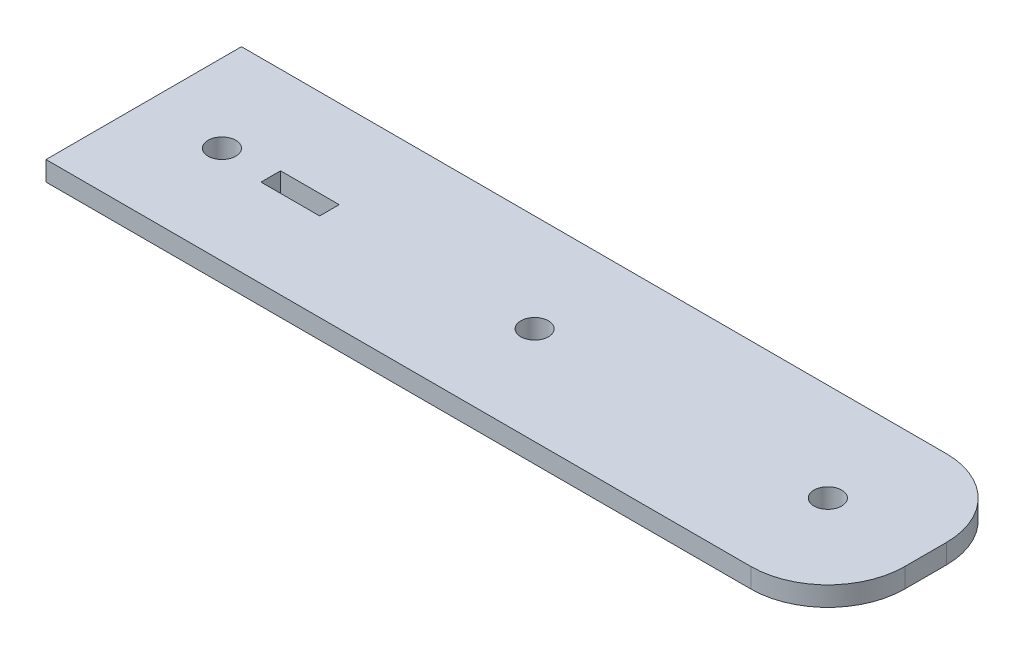
SolidWorks part; units mm, degrees
ref_plane "Front Plane" through (0, 0, 0) normal (0, 0, 1) x (1, 0, 0)
ref_plane "Top Plane" through (0, 0, 0) normal (0, 1, 0) x (1, 0, 0)
ref_plane "Right Plane" through (0, 0, 0) normal (1, 0, 0) x (0, 0, -1)
sketch "Sketch1" plane through (0, 0, 0) normal (0, 1, 0) x (1, 0, 0)
  line L1 (-12.7, -15.875) -> (101.8, -15.875)
  line L2 (-12.7, -15.875) -> (-12.7, 15.875)
  line L3 (-12.7, 15.875) -> (101.8, 15.875)
  line L4 (114.3, -3.375) -> (114.3, 3.375)
  line L5 (-12.7, -15.875) -> (114.3, 15.875) construction
  line L6 (-12.7, 15.875) -> (114.3, -15.875) construction
  line L7 (7.9375, -1.5875) -> (17.4625, -1.5875)
  line L8 (7.9375, -1.5875) -> (7.9375, 1.5875)
  line L9 (7.9375, 1.5875) -> (17.4625, 1.5875)
  line L10 (17.4625, -1.5875) -> (17.4625, 1.5875)
  line L11 (7.9375, -1.5875) -> (17.4625, 1.5875) construction
  line L12 (7.9375, 1.5875) -> (17.4625, -1.5875) construction
  circle A0 centre (0, 0) radius 2.25
  circle A1 centre (98.425, 0) radius 2.25
  arc A2 (101.8, -15.875) -> (114.3, -3.375) centre (101.8, -3.375) ccw
  arc A3 (101.8, 15.875) -> (114.3, 3.375) centre (101.8, 3.375) cw
  circle A4 centre (50.8, 0) radius 2.25
  point P0 (50.8, 0)
  point P10 (0, 0)
  point P19 (12.7, 0)
  dimension "D4" = 4.5
  dimension "D5" = 4.5
  dimension "D7" = 12.5
  dimension "D1" = 114.3
  dimension "D2" = 12.7
  dimension "D3" = 31.75
  dimension "D6" = 15.875
  dimension "D8" = 50.8
  dimension "D9" = 3.175
  dimension "D10" = 9.525
  dimension "D11" = 12.7
extrude "Boss-Extrude1" add sketch "Sketch1" along normal blind 3.175
